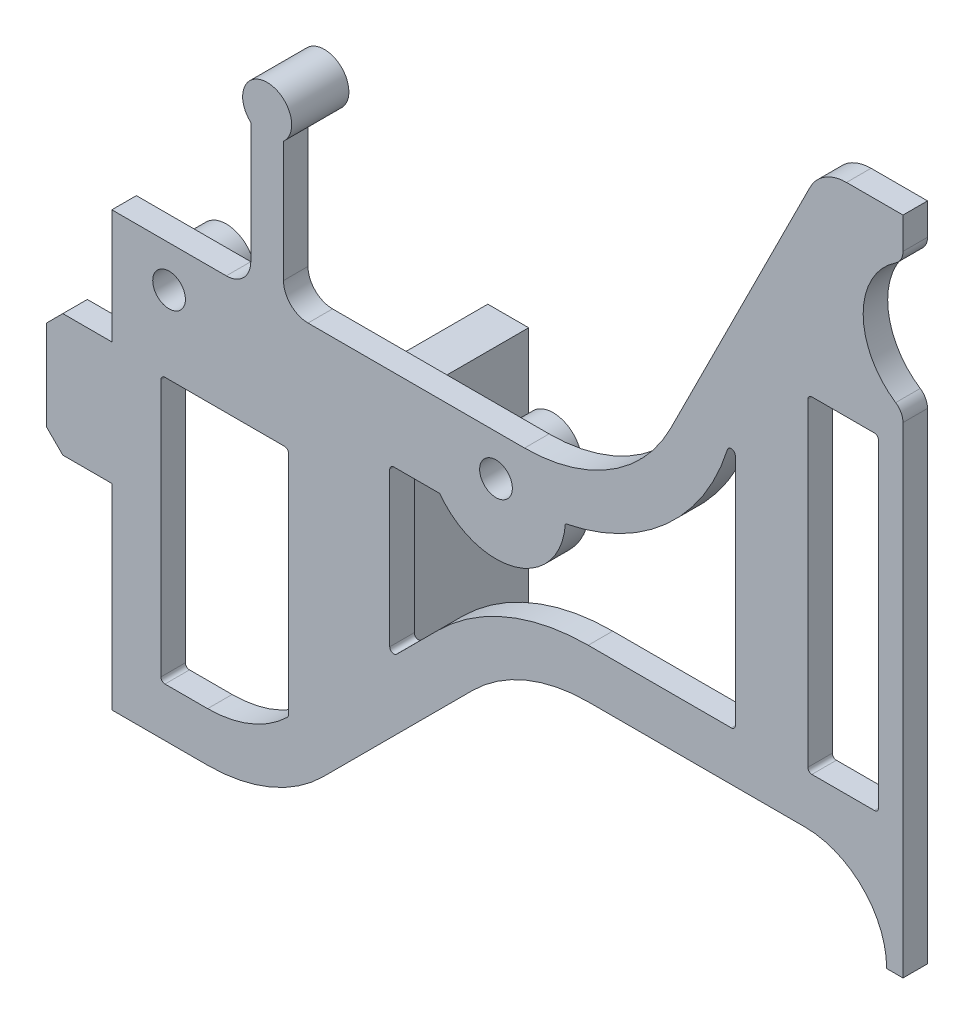
SolidWorks part; units mm, degrees
material "PE Low/Medium Density"
ref_plane "Front Plane" through (0, 0, 0) normal (0, 0, 1) x (1, 0, 0)
ref_plane "Top Plane" through (0, 0, 0) normal (0, 1, 0) x (1, 0, 0)
ref_plane "Right Plane" through (0, 0, 0) normal (1, 0, 0) x (0, 0, -1)
sketch "Sketch1" plane through (0, 0, 0) normal (0, 0, 1) x (1, 0, 0)
  line L0 (-10.15, 83.4441) -> (-10.15, 88.4441)
  line L1 (-10.15, 93.0432) -> (-10.15, 83.4441) construction
  line L2 (-10.15, 67.5991) -> (-10.15, 17.5991)
  line L3 (-10.15, 67.5991) -> (-10.15, -66.5559) construction
  line L4 (-10.15, 88.4441) -> (-20.15, 88.4441)
  line L5 (-20.15, 88.4441) -> (-44.1, 40.6)
  line L6 (-44.1, 40.6) -> (-106.95, 40.6)
  line L7 (-106.95, 40.6) -> (-106.95, 17.5991)
  line L8 (-106.95, 17.5991) -> (-10.15, 17.5991)
  line L9 (-6.95, 80.6) -> (-106.95, 80.6) construction
  line L10 (-29.1, 0) -> (-29.1, 79) construction
  line L11 (-106.95, 80.6) -> (-106.95, 40.6) construction
  line L12 (-99.95, 35.6) -> (-59.95, 35.6) construction
  circle A0 centre (-6.15, 75.5216) radius 8.875 construction
  arc A1 (-10.15, 83.4441) -> (-10.15, 67.5991) centre (-6.15, 75.5216) ccw
  circle A2 centre (-99.95, 35.6) radius 2
  circle A3 centre (-59.95, 35.6) radius 2
  dimension "D7" = 4
  dimension "D9" = 5
  dimension "D1" = 5
  dimension "D2" = 50
  dimension "D3" = 40
  dimension "D4" = 15
  dimension "D5" = 10
  dimension "D6" = 40
  dimension "D8" = 5
extrude "Boss-Extrude2" add sketch "Sketch1" along normal blind 3
fillet "Fillet1" radius 20 1 edges at (-44.1, 40.6, 1.5)
fillet "Fillet2" radius 5 1 edges at (-20.15, 88.4441, 1.5)
fillet "Fillet3" radius 2 2 edges at (-10.15, 67.5991, 1.5) (-10.15, 83.4441, 1.5)
sketch "Sketch2" plane through (0, 0, 3) normal (0, 0, 1) x (1, 0, 0)
  line L0 (-106.95, 17.5991) -> (-106.95, -12.4009)
  line L1 (-106.95, -12.4009) -> (-86.95, -12.4009)
  line L2 (-86.95, -12.4009) -> (-56.95, 17.5991)
  line L3 (-106.95, 17.5991) -> (-10.15, 17.5991) construction
  line L4 (-106.95, 17.5991) -> (-56.95, 17.5991)
  dimension "D1" = 30
  dimension "D2" = 20
  dimension "D3" = 50
extrude "Boss-Extrude3" add sketch "Sketch2" against normal up to surface (3 mm away) up to face at (-34.3828, 60.8998, 0)
fillet "Fillet4" radius 20 2 edges at (-86.95, -12.4009, 1.5)
sketch "Sketch3" plane through (0, 0, 0) normal (0, 0, -1) x (-1, 0, 0)
  line L0 (24.8, 17.5991) -> (24.8, 62.5991)
  line L1 (48.6657, 17.5991) -> (10.15, 17.5991) construction
  line L2 (24.8, 62.5991) -> (26.8, 62.5991)
  line L3 (26.8, 62.5991) -> (26.8, 17.5991)
  line L4 (26.8, 17.5991) -> (24.8, 17.5991)
  line L5 (24.8, 77.3932) -> (24.8, -25) construction
  dimension "D1" = 2
  dimension "D2" = 45
extrude "Boss-Extrude4" add sketch "Sketch3" along normal blind 2
sketch "Sketch4" plane through (0, 0, 0) normal (0, 0, -1) x (-1, 0, 0)
  circle A0 centre (99.95, 35.6) radius 2 construction
  circle A1 centre (59.95, 35.6) radius 2 construction
  circle A2 centre (99.95, 35.6) radius 2
  circle A3 centre (59.95, 35.6) radius 2
  circle A4 centre (99.95, 35.6) radius 3.5
  circle A5 centre (59.95, 35.6) radius 3.5
  dimension "D1" = 7
extrude "Boss-Extrude5" add sketch "Sketch4" along normal blind 4
sketch "Sketch5" plane through (0, 0, 3) normal (0, 0, 1) x (1, 0, 0)
  line L0 (-106.95, 40.6) -> (-106.95, -12.4009) construction
  line L1 (-106.95, 11.6) -> (-114.95, 11.6)
  line L2 (-106.95, 11.6) -> (-106.95, 26.6)
  line L3 (-106.95, 26.6) -> (-114.95, 26.6)
  line L4 (-114.95, 11.6) -> (-114.95, 26.6)
  line L5 (-56.4542, 40.6) -> (-106.95, 40.6) construction
  dimension "D1" = 15
  dimension "D2" = 8
  dimension "D3" = 14
extrude "Boss-Extrude6" add sketch "Sketch5" against normal up to surface (3 mm away) up to face at (-96.45, 35.6, 0)
chamfer "Chamfer1" distance 2 angle 45 2 edges at (-114.95, 26.6, 1.5) (-114.95, 11.6, 1.5)
sketch "Sketch6" plane through (0, 0, 3) normal (0, 0, 1) x (1, 0, 0)
  line L0 (-10.15, 17.5991) -> (-10.15, 7.5991)
  line L1 (-10.15, 67.5991) -> (-10.15, -66.5559) construction
  line L2 (-10.15, 7.5991) -> (-12.15, 7.5991)
  line L3 (-48.6657, 17.5991) -> (-10.15, 17.5991) construction
  line L4 (-22.15, 17.5991) -> (-10.15, 17.5991)
  arc A0 (-12.15, 7.5991) -> (-22.15, 17.5991) centre (-22.15, 7.5991) ccw
  dimension "D1" = 10
  dimension "D2" = 2
extrude "Boss-Extrude7" add sketch "Sketch6" against normal up to surface (3 mm away) up to face at (-96.45, 35.6, 0)
sketch "Sketch7" plane through (0, 0, 3) normal (0, 0, 1) x (1, 0, 0)
  line L0 (-85.95, 40.6) -> (-85.95, 58.3639)
  line L1 (-56.4542, 40.6) -> (-106.95, 40.6) construction
  line L2 (-85.95, 40.6) -> (-89.95, 40.6)
  line L3 (-89.95, 40.6) -> (-89.95, 58.3639)
  arc A0 (-89.95, 58.3639) -> (-85.95, 58.3639) centre (-87.95, 60.6) cw
  circle A1 centre (-99.95, 35.6) radius 2 construction
  dimension "D4" = 3
  dimension "D1" = 10
  dimension "D2" = 25
  dimension "D3" = 4
extrude "Boss-Extrude8" add sketch "Sketch7" against normal up to surface (3 mm away) up to face at (-96.45, 35.6, 0)
fillet "Fillet5" radius 3 2 edges at (-85.95, 40.6, 1.5) (-89.95, 40.6, 1.5)
sketch "Sketch8" plane through (0, 0, 0) normal (0, 0, -1) x (-1, 0, 0)
  circle A0 centre (87.95, 60.6) radius 3
extrude "Boss-Extrude9" add sketch "Sketch8" along normal up to surface (4 mm away) up to face at (-103.45, 35.6, -4)
sketch "Sketch9" plane through (0, 0, 0) normal (0, 0, -1) x (-1, 0, 0)
  line L0 (106.95, 40.6) -> (106.95, 26.6) construction
  line L1 (81.95, -1.4) -> (78.95, -1.4)
  line L2 (78.95, -1.4) -> (78.95, 30.6)
  line L3 (83.95, 30.6) -> (78.95, 30.6)
  line L5 (80.95, 29.1) -> (81.95, -1.4)
  line L6 (83.95, 30.6) -> (83.95, 29.1)
  line L7 (83.95, 29.1) -> (80.95, 29.1)
  line L8 (106.95, 11.6) -> (106.95, -12.4009) construction
  circle A1 centre (99.95, 35.6) radius 3.5 construction
  circle A2 centre (99.95, 35.6) radius 3.5 construction
  dimension "D2" = 1.5
  dimension "D1" = 26
  dimension "D3" = 32
  dimension "D4" = 25
  dimension "D5" = 5
  dimension "D6" = 1.5
  dimension "D7" = 2
extrude "Boss-Extrude10" add sketch "Sketch9" along normal blind 20
fillet "Fillet6" radius 2 1 edges at (-78.95, 14.6, 0)
sketch "Sketch10" plane through (0, 0, 0) normal (0, 0, -1) x (-1, 0, 0)
  line L0 (100.95, 26.1) -> (85.3348, 26.1)
  line L1 (85.3348, 26.1) -> (85.3348, -2.3004)
  line L2 (95.2343, -6.4009) -> (100.95, -6.4009)
  line L3 (100.95, -6.4009) -> (100.95, 26.1)
  line L4 (106.95, 11.6) -> (106.95, -12.4009) construction
  line L5 (72.95, 30.6) -> (76.95, 30.6) construction
  line L6 (30.6657, 57.2904) -> (30.6657, 23.5991)
  line L7 (30.6657, 23.5991) -> (48.6657, 23.5991)
  line L8 (67.0505, 15.9839) -> (72.95, 10.0844)
  line L9 (72.95, 10.0844) -> (72.95, 30.6)
  line L10 (72.95, 30.6) -> (66.8239, 30.6)
  line L12 (78.95, 30.6) -> (78.95, -1.4) construction
  circle A1 centre (99.95, 35.6) radius 3.5 construction
  arc A2 (85.3348, -2.3004) -> (95.2343, -6.4009) centre (95.2343, 7.5991) ccw
  arc A3 (85.3348, -2.3004) -> (95.2343, -6.4009) centre (95.2343, 7.5991) ccw
  arc A12 (33.2046, 48.9616) -> (56.4542, 34.6) centre (56.4542, 60.6) ccw
  arc A13 (30.6657, 57.2904) -> (51.4657, 35.083) centre (56.4542, 60.6) ccw
  arc A15 (67.0505, 15.9839) -> (48.6657, 23.5991) centre (48.6657, -2.4009) ccw
  arc A16 (67.0505, 15.9839) -> (48.6657, 23.5991) centre (48.6657, -2.4009) ccw
  circle A18 centre (59.95, 35.6) radius 8.5
  arc A19 (51.4657, 35.083) -> (66.8239, 30.6) centre (59.95, 35.6) ccw
  dimension "D1" = 6
  dimension "D2" = 6
  dimension "D3" = 6
  dimension "D4" = 6
  dimension "D6" = 5
  dimension "D7" = 6
  dimension "D8" = 18
  dimension "D5" = 6
extrude "Cut-Extrude1" cut sketch "Sketch10" against normal through all
sketch "Sketch11" plane through (0, 0, 3) normal (0, 0, 1) x (1, 0, 0)
  line L0 (-21.8, 23.5991) -> (-30.6657, 23.5991) construction
  line L1 (-21.8, 23.5991) -> (-13.15, 23.5991)
  line L2 (-21.8, 23.5991) -> (-21.8, 63.5991)
  line L3 (-21.8, 63.5991) -> (-13.15, 63.5991)
  line L4 (-13.15, 23.5991) -> (-13.15, 63.5991)
  line L5 (-10.15, 7.5991) -> (-10.15, 66.4516) construction
  line L6 (-24.8, 77.3932) -> (-24.8, -25) construction
  dimension "D1" = 3
  dimension "D2" = 3
  dimension "D3" = 40
extrude "Cut-Extrude2" cut sketch "Sketch11" against normal through all
fillet "Fillet7" radius 0.5 12 edges at (-30.6657, 23.5991, 1.5) (-30.6657, 57.2904, 1.5) (-72.95, 30.6, 1.5) (-72.95, 10.0844, 1.5) (-100.95, 26.1, 1.5) (-85.3348, 26.1, 1.5) (-85.3348, -2.3004, 1.5) (-100.95, -6.4009, 1.5) (-13.15, 23.5991, 1.5) (-21.8, 23.5991, 1.5) (-21.8, 63.5991, 1.5) (-13.15, 63.5991, 1.5)
